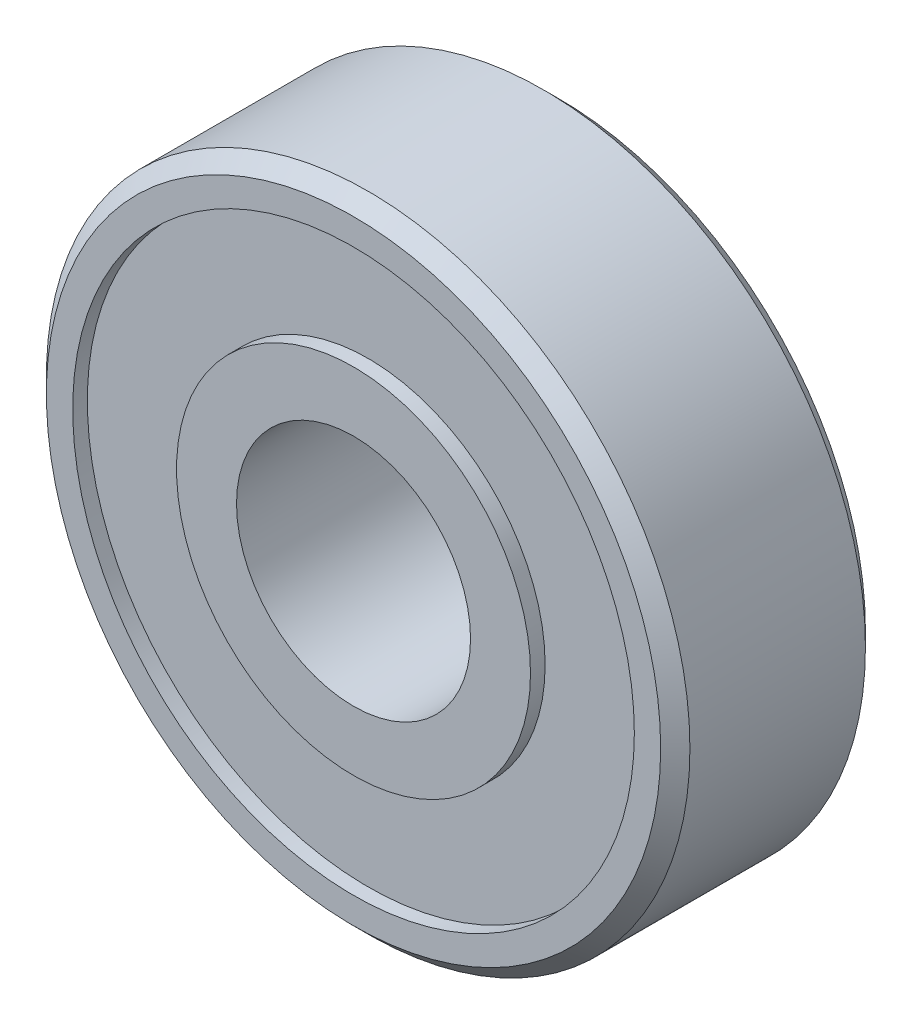
SolidWorks part; units mm, degrees
ref_plane "정면" through (0, 0, 0) normal (0, 0, 1) x (1, 0, 0)
ref_plane "윗면" through (0, 0, 0) normal (0, 1, 0) x (1, 0, 0)
ref_plane "우측면" through (0, 0, 0) normal (1, 0, 0) x (0, 0, -1)
sketch "스케치1" plane through (0, 0, 0) normal (0, 0, 1) x (1, 0, 0)
  circle A0 centre (0, 0) radius 11
  circle A1 centre (0, 0) radius 4
  dimension "D1" = 22
  dimension "D2" = 8
extrude "보스-돌출1" add sketch "스케치1" along normal mid plane 7
chamfer "모따기1" distance 0.5 angle 45 2 edges at (11, 0, -3.5) (11, 0, 3.5)
sketch "스케치2" plane through (0, 0, 3.5) normal (0, 0, 1) x (1, 0, 0)
  circle A0 centre (0, 0) radius 9.6
  circle A1 centre (0, 0) radius 10.5
  circle A2 centre (0, 0) radius 10.5
  circle A3 centre (0, 0) radius 6.05
  dimension "D2" = 19.2
  dimension "D3" = 12.1
  dimension "D1" = 0
extrude "컷-돌출1" cut sketch "스케치2" against normal blind 0.5 contours A0 A3 region at (-9.3285, 0, 3.5)
mirror "대칭 복사1" about plane through (0, 0, 0) normal (0, 0, 1) of "컷-돌출1"
